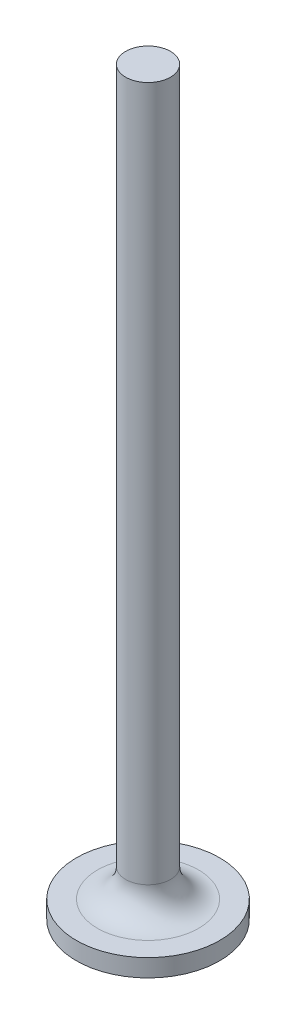
SolidWorks part; units mm, degrees
material "AISI 316 Annealed Stainless Steel Bar (SS)"
ref_plane "Front Plane" through (0, 0, 0) normal (0, 0, 1) x (1, 0, 0)
ref_plane "Top Plane" through (0, 0, 0) normal (0, 1, 0) x (1, 0, 0)
ref_plane "Right Plane" through (0, 0, 0) normal (1, 0, 0) x (0, 0, -1)
sketch "Sketch1" plane through (0, 0, 0) normal (0, 0, 1) x (1, 0, 0)
  line L0 (0, -31.8317) -> (0, 0) construction
  line L1 (0, 0) -> (10.16, 0)
  line L2 (10.16, 0) -> (10.16, 2.5)
  line L4 (3.175, 2.5) -> (3.175, 105)
  line L5 (3.175, 105) -> (0, 105)
  line L7 (0, 105) -> (0, 0)
  line L8 (10.16, 2.5) -> (3.175, 2.5)
  dimension "D1" = 10.16
  dimension "D2" = 3.175
  dimension "D3" = 2.5
  dimension "D4" = 105
revolve "Revolve1" add sketch "Sketch1" angle 360 about L0
cosmetic thread "Cosmetic Thread1" parameters "D1"=12, "D2"=5.268
sketch "Sketch2" [suppressed] plane through (0, 2.5, 0) normal (0, 1, 0) x (1, 0, 0)
  line L0 (-0.75, 10.1323) -> (-0.75, 0)
  line L1 (-0.75, 0) -> (0.75, 0)
  line L2 (0.75, 0) -> (0.75, 10.1323)
  circle A0 centre (0, 0) radius 10.16 construction
  arc A1 (0.75, 10.1323) -> (-0.75, 10.1323) centre (0, 0) ccw
  point P7 (0, 0)
  dimension "D1" = 1.5
extrude "Boss-Extrude1" [suppressed] add sketch "Sketch2" along normal blind 12
pattern_circular "CirPattern1" [suppressed] count 3 over 360 of bodies 102
sketch "Sketch3" [suppressed] plane through (0, 14.5, 0) normal (0, 1, 0) x (1, 0, 0)
  circle A0 centre (0, 0) radius 7.475
  dimension "D1" = 14.95
extrude "Cut-Extrude2" [suppressed] cut sketch "Sketch3" against normal up to surface (12 mm away) flip side to cut up to face at (0, 2.5, -3.175)
fillet "Fillet1" radius 4 1 edges at (0, 2.5, -3.175)
